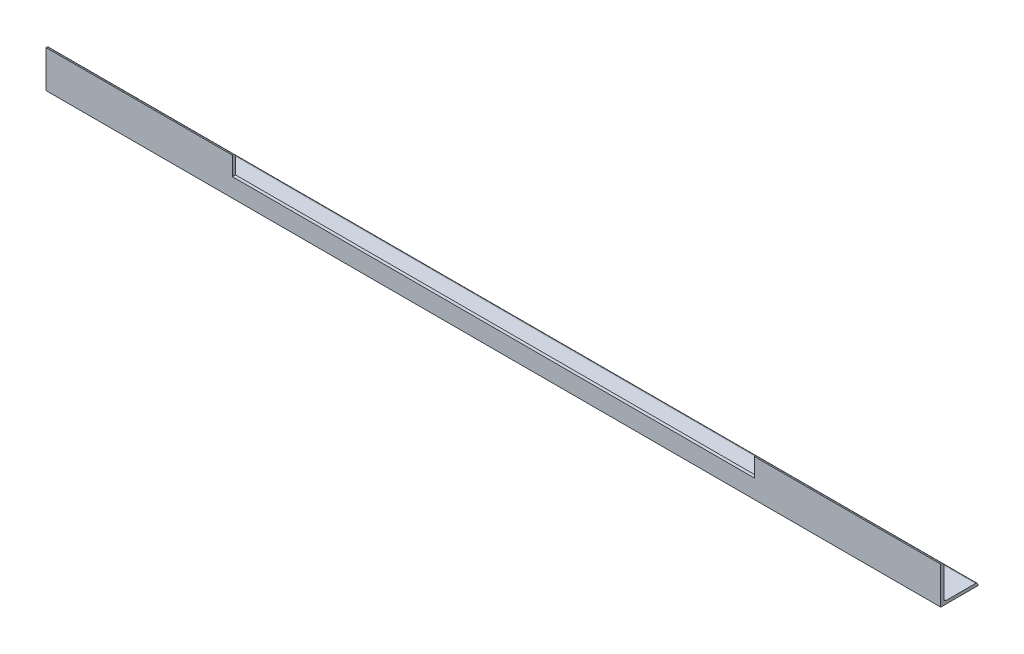
SolidWorks part; units mm, degrees
material "6063-T6"
ref_plane "Front Plane" through (0, 0, 0) normal (0, 0, 1) x (1, 0, 0)
ref_plane "Top Plane" through (0, 0, 0) normal (0, 1, 0) x (1, 0, 0)
ref_plane "Right Plane" through (0, 0, 0) normal (1, 0, 0) x (0, 0, -1)
sketch "Sketch1" plane through (0, 0, 0) normal (1, 0, 0) x (0, 0, -1)
  line L0 (0, 76.2) -> (0, 0)
  line L1 (0, 0) -> (76.2, 0)
  line L2 (6.35, 71.12) -> (6.35, 11.43)
  line L3 (11.43, 6.35) -> (71.12, 6.35)
  line L4 (0, 76.2) -> (1.27, 76.2)
  line L5 (76.2, 1.27) -> (76.2, 0)
  line L6 (6.35, 76.2) -> (6.35, 6.35) construction
  line L7 (6.35, 6.35) -> (76.2, 6.35) construction
  arc A0 (6.35, 11.43) -> (11.43, 6.35) centre (11.43, 11.43) ccw
  arc A1 (71.12, 6.35) -> (76.2, 1.27) centre (71.12, 1.27) cw
  arc A2 (6.35, 71.12) -> (1.27, 76.2) centre (1.27, 71.12) ccw
  dimension "D1" = 76.2
  dimension "D3" = 5.08
  dimension "D2" = 6.35
extrude "Boss-Extrude1" add sketch "Sketch1" along normal blind 914.4 and the other way blind 914.4
sketch "Sketch2" plane through (0, 0, 0) normal (0, 0, 1) x (1, 0, 0)
  line L0 (-914.4, 76.2) -> (914.4, 76.2) construction
  line L1 (-533.4, 76.2) -> (533.4, 76.2)
  line L2 (-533.4, 76.2) -> (-533.4, 38.1)
  line L3 (-533.4, 38.1) -> (533.4, 38.1)
  line L4 (533.4, 76.2) -> (533.4, 38.1)
  line L5 (-914.4, 76.2) -> (-914.4, 0) construction
  line L6 (-914.4, 0) -> (914.4, 0) construction
  point P8 (-914.4, 38.1)
  dimension "D1" = 381
  dimension "D2" = 1447.8
  dimension "D3" = 38.1
extrude "Cut-Extrude1" cut sketch "Sketch2" against normal through all
fillet "Fillet1" [suppressed] radius 25.4
